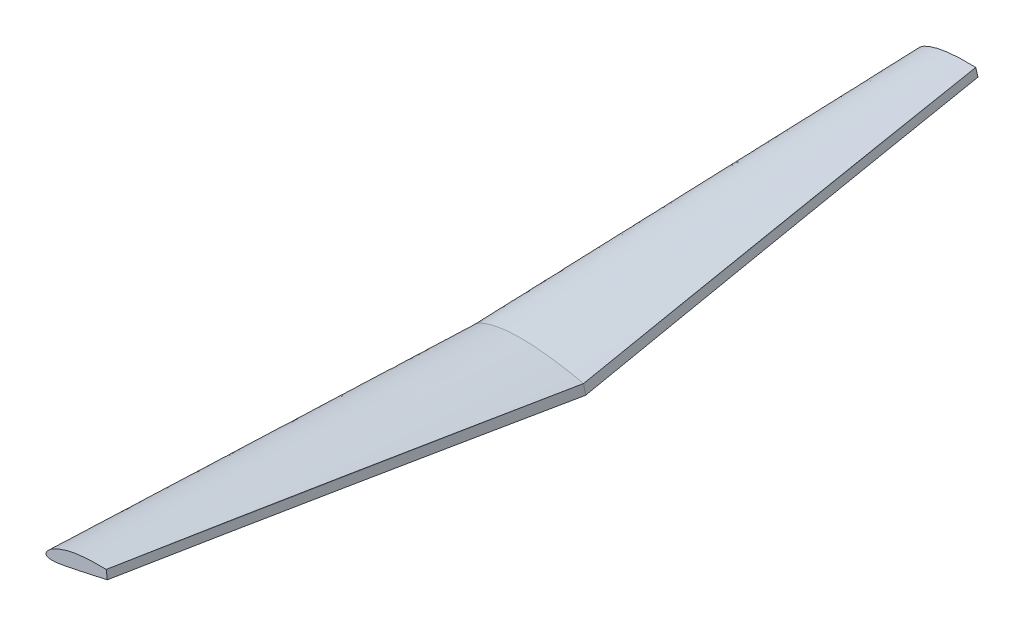
SolidWorks part; units mm, degrees
material "Polyurethane Foam Flexible"
ref_plane "Front Plane" through (0, 0, 0) normal (0, 0, 1) x (1, 0, 0)
ref_plane "Top Plane" through (0, 0, 0) normal (0, 1, 0) x (1, 0, 0)
ref_plane "Right Plane" through (0, 0, 0) normal (1, 0, 0) x (0, 0, -1)
other "Center of Mass"
curve "Curve1"
  spline degree 3 poles (25.3425, -0.0032, 0) (25.4146, -0.0017, 0) (25.3409, 0.0182, 0) (25.2821, 0.0451, 0) (25.1344, 0.0958, 0) (24.9517, 0.161, 0) (24.709, 0.2432, 0) (24.4175, 0.3367, 0) (24.0747, 0.4415, 0) (23.6834, 0.5551, 0) (23.2451, 0.6783, 0) (22.7618, 0.81, 0) (22.2354, 0.9484, 0) (21.6681, 1.0919, 0) (21.0623, 1.2389, 0) (20.4209, 1.3885, 0) (19.7464, 1.5394, 0) (19.0417, 1.6901, 0) (18.3099, 1.8386, 0) (17.5539, 1.9826, 0) (16.7773, 2.1212, 0) (15.9832, 2.2523, 0) (15.1749, 2.3749, 0) (14.3561, 2.4876, 0) (13.5301, 2.589, 0) (12.7007, 2.6789, 0) (11.8712, 2.7549, 0) (11.0452, 2.8159, 0) (10.2263, 2.8599, 0) (9.4178, 2.885, 0) (8.6235, 2.8892, 0) (7.8465, 2.8727, 0) (7.0902, 2.8342, 0) (6.3579, 2.774, 0) (5.6528, 2.6933, 0) (4.9779, 2.5936, 0) (4.3359, 2.4765, 0) (3.7299, 2.3419, 0) (3.1621, 2.1931, 0) (2.6348, 2.0323, 0) (2.15, 1.859, 0) (1.7108, 1.6713, 0) (1.3186, 1.4721, 0) (0.9759, 1.2652, 0) (0.6817, 1.0585, 0) (0.4381, 0.8519, 0) (0.2437, 0.6447, 0) (0.1056, 0.4314, 0) (0.023, 0.2224, 0) (-0.0092, 0.0288, 0) (0.0156, -0.1458, 0) (0.1079, -0.2922, 0) (0.2518, -0.4161, 0) (0.4427, -0.535, 0) (0.6865, -0.6448, 0) (0.9795, -0.749, 0) (1.3229, -0.8412, 0) (1.7153, -0.9161, 0) (2.1543, -0.9744, 0) (2.6382, -1.0177, 0) (3.165, -1.046, 0) (3.7325, -1.0605, 0) (4.3383, -1.0625, 0) (4.9798, -1.0547, 0) (5.6544, -1.0368, 0) (6.3592, -1.0098, 0) (7.0911, -0.9767, 0) (7.8469, -0.9396, 0) (8.6236, -0.9006, 0) (9.4177, -0.8609, 0) (10.2259, -0.8201, 0) (11.0447, -0.7781, 0) (11.8706, -0.7345, 0) (12.7, -0.6894, 0) (13.5294, -0.6427, 0) (14.3553, -0.5946, 0) (15.1742, -0.5462, 0) (15.9823, -0.4975, 0) (16.7764, -0.4501, 0) (17.5531, -0.4056, 0) (18.3089, -0.3633, 0) (19.0409, -0.3246, 0) (19.7457, -0.2888, 0) (20.4202, -0.2559, 0) (21.0617, -0.2255, 0) (21.6674, -0.1973, 0) (22.2347, -0.1717, 0) (22.7612, -0.1486, 0) (23.2445, -0.1279, 0) (23.6828, -0.1103, 0) (24.074, -0.0935, 0) (24.4169, -0.0769, 0) (24.7085, -0.0595, 0) (24.9513, -0.0416, 0) (25.1346, -0.0248, 0) (25.2812, -0.0133, 0) (25.3425, -0.0032, 0) (25.4146, -0.0017, 0) (25.3409, 0.0182, 0) knots -0.004677 -0.002084 -0.000521 0 0.000552 0.002207 0.004953 0.008769 0.013624 0.019492 0.026331 0.034118 0.042815 0.05238 0.06278 0.073959 0.085865 0.098446 0.111647 0.125415 0.139681 0.154378 0.169447 0.184821 0.200433 0.216224 0.232117 0.248051 0.26396 0.279777 0.295442 0.310885 0.326054 0.340892 0.355349 0.369378 0.38293 0.395953 0.40841 0.420261 0.431467 0.441988 0.451799 0.46091 0.469304 0.476946 0.483798 0.489858 0.495198 0.499997 0.504304 0.507974 0.511123 0.514149 0.51765 0.521912 0.526982 0.532916 0.539692 0.547309 0.555757 0.565025 0.575098 0.58594 0.597509 0.609762 0.622649 0.636122 0.650118 0.664572 0.679425 0.694613 0.710068 0.725733 0.741529 0.757395 0.773262 0.789063 0.804734 0.820197 0.835393 0.850252 0.864712 0.878713 0.892194 0.905092 0.917358 0.92894 0.939788 0.949856 0.959093 0.967472 0.974955 0.981503 0.987099 0.99171 0.995323 0.997916 0.999479 1 1.000552 1.002207 1.004953 periodic
sketch "Sketch10" plane through (0, 0, 0) normal (0, 0, 1) x (1, 0, 0)
  spline S0 degree 3 poles (25.3425, -0.0032) (25.4146, -0.0017) (25.3409, 0.0182) (25.2821, 0.0451) (25.1344, 0.0958) (24.9517, 0.161) (24.709, 0.2432) (24.4175, 0.3367) (24.0747, 0.4415) (23.6834, 0.5551) (23.2451, 0.6783) (22.7618, 0.81) (22.2354, 0.9484) (21.6681, 1.0919) (21.0623, 1.2389) (20.4209, 1.3885) (19.7464, 1.5394) (19.0417, 1.6901) (18.3099, 1.8386) (17.5539, 1.9826) (16.7773, 2.1212) (15.9832, 2.2523) (15.1749, 2.3749) (14.3561, 2.4876) (13.5301, 2.589) (12.7007, 2.6789) (11.8712, 2.7549) (11.0452, 2.8159) (10.2263, 2.8599) (9.4178, 2.885) (8.6235, 2.8892) (7.8465, 2.8727) (7.0902, 2.8342) (6.3579, 2.774) (5.6528, 2.6933) (4.9779, 2.5936) (4.3359, 2.4765) (3.7299, 2.3419) (3.1621, 2.1931) (2.6348, 2.0323) (2.15, 1.859) (1.7108, 1.6713) (1.3186, 1.4721) (0.9759, 1.2652) (0.6817, 1.0585) (0.4381, 0.8519) (0.2437, 0.6447) (0.1056, 0.4314) (0.023, 0.2224) (-0.0092, 0.0288) (0.0156, -0.1458) (0.1079, -0.2922) (0.2518, -0.4161) (0.4427, -0.535) (0.6865, -0.6448) (0.9795, -0.749) (1.3229, -0.8412) (1.7153, -0.9161) (2.1543, -0.9744) (2.6382, -1.0177) (3.165, -1.046) (3.7325, -1.0605) (4.3383, -1.0625) (4.9798, -1.0547) (5.6544, -1.0368) (6.3592, -1.0098) (7.0911, -0.9767) (7.8469, -0.9396) (8.6236, -0.9006) (9.4177, -0.8609) (10.2259, -0.8201) (11.0447, -0.7781) (11.8706, -0.7345) (12.7, -0.6894) (13.5294, -0.6427) (14.3553, -0.5946) (15.1742, -0.5462) (15.9823, -0.4975) (16.7764, -0.4501) (17.5531, -0.4056) (18.3089, -0.3633) (19.0409, -0.3246) (19.7457, -0.2888) (20.4202, -0.2559) (21.0617, -0.2255) (21.6674, -0.1973) (22.2347, -0.1717) (22.7612, -0.1486) (23.2445, -0.1279) (23.6828, -0.1103) (24.074, -0.0935) (24.4169, -0.0769) (24.7085, -0.0595) (24.9513, -0.0416) (25.1346, -0.0248) (25.2812, -0.0133) (25.3425, -0.0032) (25.4146, -0.0017) (25.3409, 0.0182) knots -0.004677 -0.002084 -0.000521 0 0.000552 0.002207 0.004953 0.008769 0.013624 0.019492 0.026331 0.034118 0.042815 0.05238 0.06278 0.073959 0.085865 0.098446 0.111647 0.125415 0.139681 0.154378 0.169447 0.184821 0.200433 0.216224 0.232117 0.248051 0.26396 0.279777 0.295442 0.310885 0.326054 0.340892 0.355349 0.369378 0.38293 0.395953 0.40841 0.420261 0.431467 0.441988 0.451799 0.46091 0.469304 0.476946 0.483798 0.489858 0.495198 0.499997 0.504304 0.507974 0.511123 0.514149 0.51765 0.521912 0.526982 0.532916 0.539692 0.547309 0.555757 0.565025 0.575098 0.58594 0.597509 0.609762 0.622649 0.636122 0.650118 0.664572 0.679425 0.694613 0.710068 0.725733 0.741529 0.757395 0.773262 0.789063 0.804734 0.820197 0.835393 0.850252 0.864712 0.878713 0.892194 0.905092 0.917358 0.92894 0.939788 0.949856 0.959093 0.967472 0.974955 0.981503 0.987099 0.99171 0.995323 0.997916 0.999479 1 1.000552 1.002207 1.004953 only from (25.4, 0) to (25.4, 0) construction
  spline S1 degree 3 poles (25.3425, -0.0032) (25.4146, -0.0017) (25.3409, 0.0182) (25.2821, 0.0451) (25.1344, 0.0958) (24.9517, 0.161) (24.709, 0.2432) (24.4175, 0.3367) (24.0747, 0.4415) (23.6834, 0.5551) (23.2451, 0.6783) (22.7618, 0.81) (22.2354, 0.9484) (21.6681, 1.0919) (21.0623, 1.2389) (20.4209, 1.3885) (19.7464, 1.5394) (19.0417, 1.6901) (18.3099, 1.8386) (17.5539, 1.9826) (16.7773, 2.1212) (15.9832, 2.2523) (15.1749, 2.3749) (14.3561, 2.4876) (13.5301, 2.589) (12.7007, 2.6789) (11.8712, 2.7549) (11.0452, 2.8159) (10.2263, 2.8599) (9.4178, 2.885) (8.6235, 2.8892) (7.8465, 2.8727) (7.0902, 2.8342) (6.3579, 2.774) (5.6528, 2.6933) (4.9779, 2.5936) (4.3359, 2.4765) (3.7299, 2.3419) (3.1621, 2.1931) (2.6348, 2.0323) (2.15, 1.859) (1.7108, 1.6713) (1.3186, 1.4721) (0.9759, 1.2652) (0.6817, 1.0585) (0.4381, 0.8519) (0.2437, 0.6447) (0.1056, 0.4314) (0.023, 0.2224) (-0.0092, 0.0288) (0.0156, -0.1458) (0.1079, -0.2922) (0.2518, -0.4161) (0.4427, -0.535) (0.6865, -0.6448) (0.9795, -0.749) (1.3229, -0.8412) (1.7153, -0.9161) (2.1543, -0.9744) (2.6382, -1.0177) (3.165, -1.046) (3.7325, -1.0605) (4.3383, -1.0625) (4.9798, -1.0547) (5.6544, -1.0368) (6.3592, -1.0098) (7.0911, -0.9767) (7.8469, -0.9396) (8.6236, -0.9006) (9.4177, -0.8609) (10.2259, -0.8201) (11.0447, -0.7781) (11.8706, -0.7345) (12.7, -0.6894) (13.5294, -0.6427) (14.3553, -0.5946) (15.1742, -0.5462) (15.9823, -0.4975) (16.7764, -0.4501) (17.5531, -0.4056) (18.3089, -0.3633) (19.0409, -0.3246) (19.7457, -0.2888) (20.4202, -0.2559) (21.0617, -0.2255) (21.6674, -0.1973) (22.2347, -0.1717) (22.7612, -0.1486) (23.2445, -0.1279) (23.6828, -0.1103) (24.074, -0.0935) (24.4169, -0.0769) (24.7085, -0.0595) (24.9513, -0.0416) (25.1346, -0.0248) (25.2812, -0.0133) (25.3425, -0.0032) (25.4146, -0.0017) (25.3409, 0.0182) knots -0.004677 -0.002084 -0.000521 0 0.000552 0.002207 0.004953 0.008769 0.013624 0.019492 0.026331 0.034118 0.042815 0.05238 0.06278 0.073959 0.085865 0.098446 0.111647 0.125415 0.139681 0.154378 0.169447 0.184821 0.200433 0.216224 0.232117 0.248051 0.26396 0.279777 0.295442 0.310885 0.326054 0.340892 0.355349 0.369378 0.38293 0.395953 0.40841 0.420261 0.431467 0.441988 0.451799 0.46091 0.469304 0.476946 0.483798 0.489858 0.495198 0.499997 0.504304 0.507974 0.511123 0.514149 0.51765 0.521912 0.526982 0.532916 0.539692 0.547309 0.555757 0.565025 0.575098 0.58594 0.597509 0.609762 0.622649 0.636122 0.650118 0.664572 0.679425 0.694613 0.710068 0.725733 0.741529 0.757395 0.773262 0.789063 0.804734 0.820197 0.835393 0.850252 0.864712 0.878713 0.892194 0.905092 0.917358 0.92894 0.939788 0.949856 0.959093 0.967472 0.974955 0.981503 0.987099 0.99171 0.995323 0.997916 0.999479 1 1.000552 1.002207 1.004953 only from (25.4, 0) to (25.4, 0) construction
ref_plane "Plane2" through (0, 0, 0) normal (0, 0.0698, 0.9976) x (1, 0, 0)
sketch "Sketch11" plane through (0, 0, 0) normal (0, 0.0698, 0.9976) x (1, 0, 0)
  spline S0 degree 3 poles (25.3425, -0.0032) (25.4146, -0.0017) (25.3409, 0.0182) (25.2821, 0.0451) (25.1344, 0.0958) (24.9517, 0.161) (24.709, 0.2432) (24.4175, 0.3367) (24.0747, 0.4415) (23.6834, 0.5551) (23.2451, 0.6783) (22.7618, 0.81) (22.2354, 0.9484) (21.6681, 1.0919) (21.0623, 1.2389) (20.4209, 1.3885) (19.7464, 1.5394) (19.0417, 1.6901) (18.3099, 1.8386) (17.5539, 1.9826) (16.7773, 2.1212) (15.9832, 2.2523) (15.1749, 2.3749) (14.3561, 2.4876) (13.5301, 2.589) (12.7007, 2.6789) (11.8712, 2.7549) (11.0452, 2.8159) (10.2263, 2.8599) (9.4178, 2.885) (8.6235, 2.8892) (7.8465, 2.8727) (7.0902, 2.8342) (6.3579, 2.774) (5.6528, 2.6933) (4.9779, 2.5936) (4.3359, 2.4765) (3.7299, 2.3419) (3.1621, 2.1931) (2.6348, 2.0323) (2.15, 1.859) (1.7108, 1.6713) (1.3186, 1.4721) (0.9759, 1.2652) (0.6817, 1.0585) (0.4381, 0.8519) (0.2437, 0.6447) (0.1056, 0.4314) (0.023, 0.2224) (-0.0092, 0.0288) (0.0156, -0.1458) (0.1079, -0.2922) (0.2518, -0.4161) (0.4427, -0.535) (0.6865, -0.6448) (0.9795, -0.749) (1.3229, -0.8412) (1.7153, -0.9161) (2.1543, -0.9744) (2.6382, -1.0177) (3.165, -1.046) (3.7325, -1.0605) (4.3383, -1.0625) (4.9798, -1.0547) (5.6544, -1.0368) (6.3592, -1.0098) (7.0911, -0.9767) (7.8469, -0.9396) (8.6236, -0.9006) (9.4177, -0.8609) (10.2259, -0.8201) (11.0447, -0.7781) (11.8706, -0.7345) (12.7, -0.6894) (13.5294, -0.6427) (14.3553, -0.5946) (15.1742, -0.5462) (15.9823, -0.4975) (16.7764, -0.4501) (17.5531, -0.4056) (18.3089, -0.3633) (19.0409, -0.3246) (19.7457, -0.2888) (20.4202, -0.2559) (21.0617, -0.2255) (21.6674, -0.1973) (22.2347, -0.1717) (22.7612, -0.1486) (23.2445, -0.1279) (23.6828, -0.1103) (24.074, -0.0935) (24.4169, -0.0769) (24.7085, -0.0595) (24.9513, -0.0416) (25.1346, -0.0248) (25.2812, -0.0133) (25.3425, -0.0032) (25.4146, -0.0017) (25.3409, 0.0182) knots -0.004677 -0.002084 -0.000521 0 0.000552 0.002207 0.004953 0.008769 0.013624 0.019492 0.026331 0.034118 0.042815 0.05238 0.06278 0.073959 0.085865 0.098446 0.111647 0.125415 0.139681 0.154378 0.169447 0.184821 0.200433 0.216224 0.232117 0.248051 0.26396 0.279777 0.295442 0.310885 0.326054 0.340892 0.355349 0.369378 0.38293 0.395953 0.40841 0.420261 0.431467 0.441988 0.451799 0.46091 0.469304 0.476946 0.483798 0.489858 0.495198 0.499997 0.504304 0.507974 0.511123 0.514149 0.51765 0.521912 0.526982 0.532916 0.539692 0.547309 0.555757 0.565025 0.575098 0.58594 0.597509 0.609762 0.622649 0.636122 0.650118 0.664572 0.679425 0.694613 0.710068 0.725733 0.741529 0.757395 0.773262 0.789063 0.804734 0.820197 0.835393 0.850252 0.864712 0.878713 0.892194 0.905092 0.917358 0.92894 0.939788 0.949856 0.959093 0.967472 0.974955 0.981503 0.987099 0.99171 0.995323 0.997916 0.999479 1 1.000552 1.002207 1.004953 only from (25.4, 0) to (25.4, 0) construction
  spline S1 degree 3 poles (163.6236, -0.0254) (164.2008, -0.0135) (163.6115, 0.1457) (163.1411, 0.3606) (161.9594, 0.7661) (160.4975, 1.2878) (158.5563, 1.9454) (156.2239, 2.6938) (153.4816, 3.5317) (150.3509, 4.4411) (146.8445, 5.4261) (142.9784, 6.4796) (138.7672, 7.587) (134.2287, 8.7351) (129.3828, 9.9109) (124.2514, 11.1077) (118.8554, 12.3152) (113.2179, 13.5209) (107.3629, 14.7088) (101.3154, 15.8607) (95.1025, 16.9698) (88.7495, 18.0186) (82.2835, 18.9995) (75.7327, 19.901) (69.1247, 20.7123) (62.4894, 21.4311) (55.8537, 22.0393) (49.2457, 22.527) (42.6941, 22.8793) (36.2266, 23.0798) (29.8718, 23.1138) (23.656, 22.9817) (17.6059, 22.6733) (11.7474, 22.1922) (6.1065, 21.5465) (0.7072, 20.7487) (-4.4284, 19.8117) (-9.2768, 18.7352) (-13.8189, 17.5445) (-18.0376, 16.2582) (-21.9157, 14.8722) (-25.4298, 13.3705) (-28.5671, 11.777) (-31.3087, 10.1219) (-33.6627, 8.4683) (-35.6112, 6.8148) (-37.1662, 5.1572) (-38.2713, 3.4515) (-38.9322, 1.779) (-39.1894, 0.2302) (-38.9912, -1.1662) (-38.2527, -2.3377) (-37.1015, -3.3287) (-35.5743, -4.2801) (-33.6243, -5.1587) (-31.2803, -5.9922) (-28.5326, -6.7295) (-25.3936, -7.3287) (-21.8814, -7.7951) (-18.0107, -8.1419) (-13.7964, -8.3682) (-9.2558, -8.4842) (-4.4093, -8.5001) (0.7228, -8.4375) (6.1194, -8.2948) (11.7573, -8.0787) (17.6126, -7.8139) (23.6594, -7.5166) (29.8724, -7.2051) (36.2252, -6.887) (42.6911, -6.5607) (49.2417, -6.2247) (55.8491, -5.8757) (62.4843, -5.5149) (69.1195, -5.1416) (75.7267, -4.7569) (82.2772, -4.3697) (88.7428, -3.9804) (95.0952, -3.6009) (101.3085, -3.245) (107.3555, -2.9061) (113.2112, -2.5966) (118.8494, -2.3107) (124.2458, -2.0471) (129.3773, -1.8043) (134.2229, -1.5783) (138.7618, -1.3734) (142.9735, -1.189) (146.8403, -1.0234) (150.3466, -0.8824) (153.4762, -0.7484) (156.2189, -0.6155) (158.5519, -0.4756) (160.4941, -0.3327) (161.9608, -0.1984) (163.1332, -0.1065) (163.6236, -0.0254) (164.2008, -0.0135) (163.6115, 0.1457) knots -0.004677 -0.002084 -0.000521 0 0.000552 0.002207 0.004953 0.008769 0.013624 0.019492 0.026331 0.034118 0.042815 0.05238 0.06278 0.073959 0.085865 0.098446 0.111647 0.125415 0.139681 0.154378 0.169447 0.184821 0.200433 0.216224 0.232117 0.248051 0.26396 0.279777 0.295442 0.310885 0.326054 0.340892 0.355349 0.369378 0.38293 0.395953 0.40841 0.420261 0.431467 0.441988 0.451799 0.46091 0.469304 0.476946 0.483798 0.489858 0.495198 0.499997 0.504304 0.507974 0.511123 0.514149 0.51765 0.521912 0.526982 0.532916 0.539692 0.547309 0.555757 0.565025 0.575098 0.58594 0.597509 0.609762 0.622649 0.636122 0.650118 0.664572 0.679425 0.694613 0.710068 0.725733 0.741529 0.757395 0.773262 0.789063 0.804734 0.820197 0.835393 0.850252 0.864712 0.878713 0.892194 0.905092 0.917358 0.92894 0.939788 0.949856 0.959093 0.967472 0.974955 0.981503 0.987099 0.99171 0.995323 0.997916 0.999479 1 1.000552 1.002207 1.004953 only from (164.084, 0) to (164.084, 0)
  point P1 (5.588, 0)
  dimension "D1" = 5.588
  dimension "D2" = 164.084
ref_plane "Plane3" through (0, 44.2954, 633.4532) normal (0, 0.0698, 0.9976) x (1, 0, 0)
sketch "Sketch12" plane through (0, 44.2954, 633.4532) normal (0, 0.0698, 0.9976) x (1, 0, 0)
  spline S1 degree 3 poles (100.2971, 14.3069) (100.6527, 14.3682) (100.2737, 14.4115) (99.9629, 14.5003) (99.1947, 14.6405) (98.2426, 14.8262) (96.9815, 15.0512) (95.4702, 15.2957) (93.6972, 15.5572) (91.6775, 15.8266) (89.4186, 16.1076) (86.931, 16.3973) (84.2251, 16.6881) (81.3131, 16.9734) (78.2086, 17.2471) (74.9257, 17.5071) (71.4783, 17.749) (67.8817, 17.9672) (64.1525, 18.1541) (60.3077, 18.3007) (56.3646, 18.4055) (52.3406, 18.4599) (48.2531, 18.4617) (44.1207, 18.4066) (39.9613, 18.2904) (35.7937, 18.1145) (31.6361, 17.8701) (27.5069, 17.5539) (23.4253, 17.1593) (19.4099, 16.6787) (15.4796, 16.1059) (11.6507, 15.4433) (7.9407, 14.6873) (4.3653, 13.8424) (0.9397, 12.9162) (-2.3223, 11.9186) (-5.4084, 10.8596) (-8.3039, 9.7412) (-10.9996, 8.5809) (-13.4864, 7.3917) (-15.7534, 6.1727) (-17.7847, 4.9163) (-19.5745, 3.6384) (-21.1141, 2.3594) (-22.4143, 1.1175) (-23.4638, -0.0865) (-24.2699, -1.2562) (-24.7934, -2.4135) (-25.0455, -3.5088) (-25.0596, -4.49) (-24.8067, -5.3344) (-24.2408, -5.9893) (-23.4368, -6.4942) (-22.4041, -6.9394) (-21.117, -7.3001) (-19.5905, -7.5961) (-17.8236, -7.7949) (-15.8278, -7.8719) (-13.6137, -7.8318) (-11.1894, -7.6844) (-8.5638, -7.4304) (-5.7471, -7.0777) (-2.7505, -6.6346) (0.415, -6.1162) (3.7367, -5.5237) (7.2006, -4.8632) (10.7942, -4.1524) (14.5032, -3.4035) (18.3136, -2.6303) (22.2097, -1.84) (26.1749, -1.0341) (30.1916, -0.2142) (34.2422, 0.619) (38.3089, 1.4621) (42.3743, 2.3129) (46.4215, 3.1681) (50.4333, 4.0196) (54.3924, 4.8644) (58.2826, 5.6927) (62.089, 6.4933) (65.7942, 7.2679) (69.3839, 8.0064) (72.8415, 8.71) (76.1517, 9.3773) (79.3001, 10.0069) (82.2735, 10.5994) (85.0592, 11.1502) (87.6447, 11.6578) (90.0188, 12.1215) (92.1724, 12.5364) (94.0939, 12.9117) (95.7764, 13.2501) (97.205, 13.5546) (98.3919, 13.8245) (99.2857, 14.0446) (100.0017, 14.2109) (100.2971, 14.3069) (100.6527, 14.3682) (100.2737, 14.4115) knots -0.004677 -0.002084 -0.000521 0 0.000552 0.002207 0.004953 0.008769 0.013624 0.019492 0.026331 0.034118 0.042815 0.05238 0.06278 0.073959 0.085865 0.098446 0.111647 0.125415 0.139681 0.154378 0.169447 0.184821 0.200433 0.216224 0.232117 0.248051 0.26396 0.279777 0.295442 0.310885 0.326054 0.340892 0.355349 0.369378 0.38293 0.395953 0.40841 0.420261 0.431467 0.441988 0.451799 0.46091 0.469304 0.476946 0.483798 0.489858 0.495198 0.499997 0.504304 0.507974 0.511123 0.514149 0.51765 0.521912 0.526982 0.532916 0.539692 0.547309 0.555757 0.565025 0.575098 0.58594 0.597509 0.609762 0.622649 0.636122 0.650118 0.664572 0.679425 0.694613 0.710068 0.725733 0.741529 0.757395 0.773262 0.789063 0.804734 0.820197 0.835393 0.850252 0.864712 0.878713 0.892194 0.905092 0.917358 0.92894 0.939788 0.949856 0.959093 0.967472 0.974955 0.981503 0.987099 0.99171 0.995323 0.997916 0.999479 1 1.000552 1.002207 1.004953 only from (100.5793, 14.3656) to (100.5793, 14.3656)
  dimension "D1" = 100.5793
  dimension "D3" = 101.6
loft "Loft3" add profiles "Sketch11", "Sketch12" connector at (164.084, 0, 0) connector at (100.5793, 58.626, 632.4511)
sketch "Sketch16" plane through (0, 44.2954, 633.4532) normal (0, 0.0698, 0.9976) x (1, 0, 0)
  line L0 (-44.2219, -15.6396) -> (132.5516, 20.9908) construction
  line L1 (60.8598, 18.2749) -> (63.2509, 6.7359)
  arc A0 (60.8598, 18.2749) -> (63.2509, 6.7359) centre (260.9448, 53.7185) cw
  spline S1 degree 3 poles (100.2971, 14.3069) (100.6527, 14.3682) (100.2737, 14.4115) (99.9629, 14.5003) (99.1947, 14.6405) (98.2426, 14.8262) (96.9815, 15.0512) (95.4702, 15.2957) (93.6972, 15.5572) (91.6775, 15.8266) (89.4186, 16.1076) (86.931, 16.3973) (84.2251, 16.6881) (81.3131, 16.9734) (78.2086, 17.2471) (74.9257, 17.5071) (71.4783, 17.749) (67.8817, 17.9672) (64.1525, 18.1541) (60.3077, 18.3007) (56.3646, 18.4055) (52.3406, 18.4599) (48.2531, 18.4617) (44.1207, 18.4066) (39.9613, 18.2904) (35.7937, 18.1145) (31.6361, 17.8701) (27.5069, 17.5539) (23.4253, 17.1593) (19.4099, 16.6787) (15.4796, 16.1059) (11.6507, 15.4433) (7.9407, 14.6873) (4.3653, 13.8424) (0.9397, 12.9162) (-2.3223, 11.9186) (-5.4084, 10.8596) (-8.3039, 9.7412) (-10.9996, 8.5809) (-13.4864, 7.3917) (-15.7534, 6.1727) (-17.7847, 4.9163) (-19.5745, 3.6384) (-21.1141, 2.3594) (-22.4143, 1.1175) (-23.4638, -0.0865) (-24.2699, -1.2562) (-24.7934, -2.4135) (-25.0455, -3.5088) (-25.0596, -4.49) (-24.8067, -5.3344) (-24.2408, -5.9893) (-23.4368, -6.4942) (-22.4041, -6.9394) (-21.117, -7.3001) (-19.5905, -7.5961) (-17.8236, -7.7949) (-15.8278, -7.8719) (-13.6137, -7.8318) (-11.1894, -7.6844) (-8.5638, -7.4304) (-5.7471, -7.0777) (-2.7505, -6.6346) (0.415, -6.1162) (3.7367, -5.5237) (7.2006, -4.8632) (10.7942, -4.1524) (14.5032, -3.4035) (18.3136, -2.6303) (22.2097, -1.84) (26.1749, -1.0341) (30.1916, -0.2142) (34.2422, 0.619) (38.3089, 1.4621) (42.3743, 2.3129) (46.4215, 3.1681) (50.4333, 4.0196) (54.3924, 4.8644) (58.2826, 5.6927) (62.089, 6.4933) (65.7942, 7.2679) (69.3839, 8.0064) (72.8415, 8.71) (76.1517, 9.3773) (79.3001, 10.0069) (82.2735, 10.5994) (85.0592, 11.1502) (87.6447, 11.6578) (90.0188, 12.1215) (92.1724, 12.5364) (94.0939, 12.9117) (95.7764, 13.2501) (97.205, 13.5546) (98.3919, 13.8245) (99.2857, 14.0446) (100.0017, 14.2109) (100.2971, 14.3069) (100.6527, 14.3682) (100.2737, 14.4115) knots -0.004677 -0.002084 -0.000521 0 0.000552 0.002207 0.004953 0.008769 0.013624 0.019492 0.026331 0.034118 0.042815 0.05238 0.06278 0.073959 0.085865 0.098446 0.111647 0.125415 0.139681 0.154378 0.169447 0.184821 0.200433 0.216224 0.232117 0.248051 0.26396 0.279777 0.295442 0.310885 0.326054 0.340892 0.355349 0.369378 0.38293 0.395953 0.40841 0.420261 0.431467 0.441988 0.451799 0.46091 0.469304 0.476946 0.483798 0.489858 0.495198 0.499997 0.504304 0.507974 0.511123 0.514149 0.51765 0.521912 0.526982 0.532916 0.539692 0.547309 0.555757 0.565025 0.575098 0.58594 0.597509 0.609762 0.622649 0.636122 0.650118 0.664572 0.679425 0.694613 0.710068 0.725733 0.741529 0.757395 0.773262 0.789063 0.804734 0.820197 0.835393 0.850252 0.864712 0.878713 0.892194 0.905092 0.917358 0.92894 0.939788 0.949856 0.959093 0.967472 0.974955 0.981503 0.987099 0.99171 0.995323 0.997916 0.999479 1 1.000552 1.002207 1.004953 only from (100.5793, 14.3656) to (100.5793, 14.3656) construction
  dimension "D2" = 203.2
  dimension "D1" = 38.1
sketch "Sketch15" plane through (0, 0, 0) normal (0, -0.0698, -0.9976) x (-1, 0, 0)
  line L0 (-122.8066, 11.4276) -> (-125.582, -1.9662)
  line L1 (-167.8103, 0.1903) -> (-164.084, 0) construction
  line L4 (-176.4673, 0.6324) -> (-164.084, 0) construction
  line L5 (-125.582, -1.9662) -> (63.3185, -11.6128) construction
  line L6 (-60.8598, 18.2749) -> (-63.2509, 6.7359) construction
  arc A0 (-122.8066, 11.4276) -> (-125.582, -1.9662) centre (-323.0547, 45.9378) ccw
  spline S0 degree 3 poles (-163.6115, 0.1457) (-164.2008, -0.0135) (-163.6236, -0.0254) (-163.1332, -0.1065) (-161.9608, -0.1984) (-160.4941, -0.3327) (-158.5519, -0.4756) (-156.2189, -0.6155) (-153.4762, -0.7484) (-150.3466, -0.8824) (-146.8403, -1.0234) (-142.9735, -1.189) (-138.7618, -1.3734) (-134.2229, -1.5783) (-129.3773, -1.8043) (-124.2458, -2.0471) (-118.8494, -2.3107) (-113.2112, -2.5966) (-107.3555, -2.9061) (-101.3085, -3.245) (-95.0952, -3.6009) (-88.7428, -3.9804) (-82.2772, -4.3697) (-75.7267, -4.7569) (-69.1195, -5.1416) (-62.4843, -5.5149) (-55.8491, -5.8757) (-49.2417, -6.2247) (-42.6911, -6.5607) (-36.2252, -6.887) (-29.8724, -7.2051) (-23.6594, -7.5166) (-17.6126, -7.8139) (-11.7573, -8.0787) (-6.1194, -8.2948) (-0.7228, -8.4375) (4.4093, -8.5001) (9.2558, -8.4842) (13.7964, -8.3682) (18.0107, -8.1419) (21.8814, -7.7951) (25.3936, -7.3287) (28.5326, -6.7295) (31.2803, -5.9922) (33.6243, -5.1587) (35.5743, -4.2801) (37.1015, -3.3287) (38.2527, -2.3377) (38.9912, -1.1662) (39.1894, 0.2302) (38.9322, 1.779) (38.2713, 3.4515) (37.1662, 5.1572) (35.6112, 6.8148) (33.6627, 8.4683) (31.3087, 10.1219) (28.5671, 11.777) (25.4298, 13.3705) (21.9157, 14.8722) (18.0376, 16.2582) (13.8189, 17.5445) (9.2768, 18.7352) (4.4284, 19.8117) (-0.7072, 20.7487) (-6.1065, 21.5465) (-11.7474, 22.1922) (-17.6059, 22.6733) (-23.656, 22.9817) (-29.8718, 23.1138) (-36.2266, 23.0798) (-42.6941, 22.8793) (-49.2457, 22.527) (-55.8537, 22.0393) (-62.4894, 21.4311) (-69.1247, 20.7123) (-75.7327, 19.901) (-82.2835, 18.9995) (-88.7495, 18.0186) (-95.1025, 16.9698) (-101.3154, 15.8607) (-107.3629, 14.7088) (-113.2179, 13.5209) (-118.8554, 12.3152) (-124.2514, 11.1077) (-129.3828, 9.9109) (-134.2287, 8.7351) (-138.7672, 7.587) (-142.9784, 6.4796) (-146.8445, 5.4261) (-150.3509, 4.4411) (-153.4816, 3.5317) (-156.2239, 2.6938) (-158.5563, 1.9454) (-160.4975, 1.2878) (-161.9594, 0.7661) (-163.1411, 0.3606) (-163.6115, 0.1457) (-164.2008, -0.0135) (-163.6236, -0.0254) knots -0.004953 -0.002207 -0.000552 0 0.000521 0.002084 0.004677 0.00829 0.012901 0.018497 0.025045 0.032528 0.040907 0.050144 0.060212 0.07106 0.082642 0.094908 0.107806 0.121287 0.135288 0.149748 0.164607 0.179803 0.195266 0.210937 0.226738 0.242605 0.258471 0.274267 0.289932 0.305387 0.320575 0.335428 0.349882 0.363878 0.377351 0.390238 0.402491 0.41406 0.424902 0.434975 0.444243 0.452691 0.460308 0.467084 0.473018 0.478088 0.48235 0.485851 0.488877 0.492026 0.495696 0.500003 0.504802 0.510142 0.516202 0.523054 0.530696 0.53909 0.548201 0.558012 0.568533 0.579739 0.59159 0.604047 0.61707 0.630622 0.644651 0.659108 0.673946 0.689115 0.704558 0.720223 0.73604 0.751949 0.767883 0.783776 0.799567 0.815179 0.830553 0.845622 0.860319 0.874585 0.888353 0.901554 0.914135 0.926041 0.93722 0.94762 0.957185 0.965882 0.973669 0.980508 0.986376 0.991231 0.995047 0.997793 0.999448 1 1.000521 1.002084 1.004677 only from (-164.084, 0) to (-164.084, 0) construction
  spline S1 degree 3 poles (-163.6115, 0.1457) (-164.2008, -0.0135) (-163.6236, -0.0254) (-163.1332, -0.1065) (-161.9608, -0.1984) (-160.4941, -0.3327) (-158.5519, -0.4756) (-156.2189, -0.6155) (-153.4762, -0.7484) (-150.3466, -0.8824) (-146.8403, -1.0234) (-142.9735, -1.189) (-138.7618, -1.3734) (-134.2229, -1.5783) (-129.3773, -1.8043) (-124.2458, -2.0471) (-118.8494, -2.3107) (-113.2112, -2.5966) (-107.3555, -2.9061) (-101.3085, -3.245) (-95.0952, -3.6009) (-88.7428, -3.9804) (-82.2772, -4.3697) (-75.7267, -4.7569) (-69.1195, -5.1416) (-62.4843, -5.5149) (-55.8491, -5.8757) (-49.2417, -6.2247) (-42.6911, -6.5607) (-36.2252, -6.887) (-29.8724, -7.2051) (-23.6594, -7.5166) (-17.6126, -7.8139) (-11.7573, -8.0787) (-6.1194, -8.2948) (-0.7228, -8.4375) (4.4093, -8.5001) (9.2558, -8.4842) (13.7964, -8.3682) (18.0107, -8.1419) (21.8814, -7.7951) (25.3936, -7.3287) (28.5326, -6.7295) (31.2803, -5.9922) (33.6243, -5.1587) (35.5743, -4.2801) (37.1015, -3.3287) (38.2527, -2.3377) (38.9912, -1.1662) (39.1894, 0.2302) (38.9322, 1.779) (38.2713, 3.4515) (37.1662, 5.1572) (35.6112, 6.8148) (33.6627, 8.4683) (31.3087, 10.1219) (28.5671, 11.777) (25.4298, 13.3705) (21.9157, 14.8722) (18.0376, 16.2582) (13.8189, 17.5445) (9.2768, 18.7352) (4.4284, 19.8117) (-0.7072, 20.7487) (-6.1065, 21.5465) (-11.7474, 22.1922) (-17.6059, 22.6733) (-23.656, 22.9817) (-29.8718, 23.1138) (-36.2266, 23.0798) (-42.6941, 22.8793) (-49.2457, 22.527) (-55.8537, 22.0393) (-62.4894, 21.4311) (-69.1247, 20.7123) (-75.7327, 19.901) (-82.2835, 18.9995) (-88.7495, 18.0186) (-95.1025, 16.9698) (-101.3154, 15.8607) (-107.3629, 14.7088) (-113.2179, 13.5209) (-118.8554, 12.3152) (-124.2514, 11.1077) (-129.3828, 9.9109) (-134.2287, 8.7351) (-138.7672, 7.587) (-142.9784, 6.4796) (-146.8445, 5.4261) (-150.3509, 4.4411) (-153.4816, 3.5317) (-156.2239, 2.6938) (-158.5563, 1.9454) (-160.4975, 1.2878) (-161.9594, 0.7661) (-163.1411, 0.3606) (-163.6115, 0.1457) (-164.2008, -0.0135) (-163.6236, -0.0254) knots -0.004953 -0.002207 -0.000552 0 0.000521 0.002084 0.004677 0.00829 0.012901 0.018497 0.025045 0.032528 0.040907 0.050144 0.060212 0.07106 0.082642 0.094908 0.107806 0.121287 0.135288 0.149748 0.164607 0.179803 0.195266 0.210937 0.226738 0.242605 0.258471 0.274267 0.289932 0.305387 0.320575 0.335428 0.349882 0.363878 0.377351 0.390238 0.402491 0.41406 0.424902 0.434975 0.444243 0.452691 0.460308 0.467084 0.473018 0.478088 0.48235 0.485851 0.488877 0.492026 0.495696 0.500003 0.504802 0.510142 0.516202 0.523054 0.530696 0.53909 0.548201 0.558012 0.568533 0.579739 0.59159 0.604047 0.61707 0.630622 0.644651 0.659108 0.673946 0.689115 0.704558 0.720223 0.73604 0.751949 0.767883 0.783776 0.799567 0.815179 0.830553 0.845622 0.860319 0.874585 0.888353 0.901554 0.914135 0.926041 0.93722 0.94762 0.957185 0.965882 0.973669 0.980508 0.986376 0.991231 0.995047 0.997793 0.999448 1 1.000521 1.002084 1.004677 only from (-164.084, 0) to (-164.084, 0) construction
  dimension "D2" = 203.2
  dimension "D1" = 38.1
sketch "Sketch13" plane through (0, 0, 0) normal (1, 0, 0) x (0, 0, -1)
  line L1 (-0.5923, 35.1673) -> (120.6777, 35.1673)
  line L2 (-0.5923, 35.1673) -> (-0.5923, -52.1068)
  line L3 (-0.5923, -52.1068) -> (120.6777, -52.1068)
  line L4 (120.6777, 35.1673) -> (120.6777, -52.1068)
  dimension "D1" = 87.2741
  dimension "D2" = 121.27
extrude "Cut-Extrude1" cut sketch "Sketch13" against normal through all both and the other way through all
ref_plane "Plane4" through (0, 0, 0) normal (0, -0.9976, 0.0698) x (-1, 0, 0)
loft "Cut-Loft1" cut profiles "Sketch15", "Sketch16" connector at (122.8066, 11.3997, -0.7971) connector at (60.8598, 62.5257, 632.1784)
mirror "Mirror1" about plane through (-39.1171, 35.1673, 0.5923) normal (0, 0, 1) of bodies 111 106
